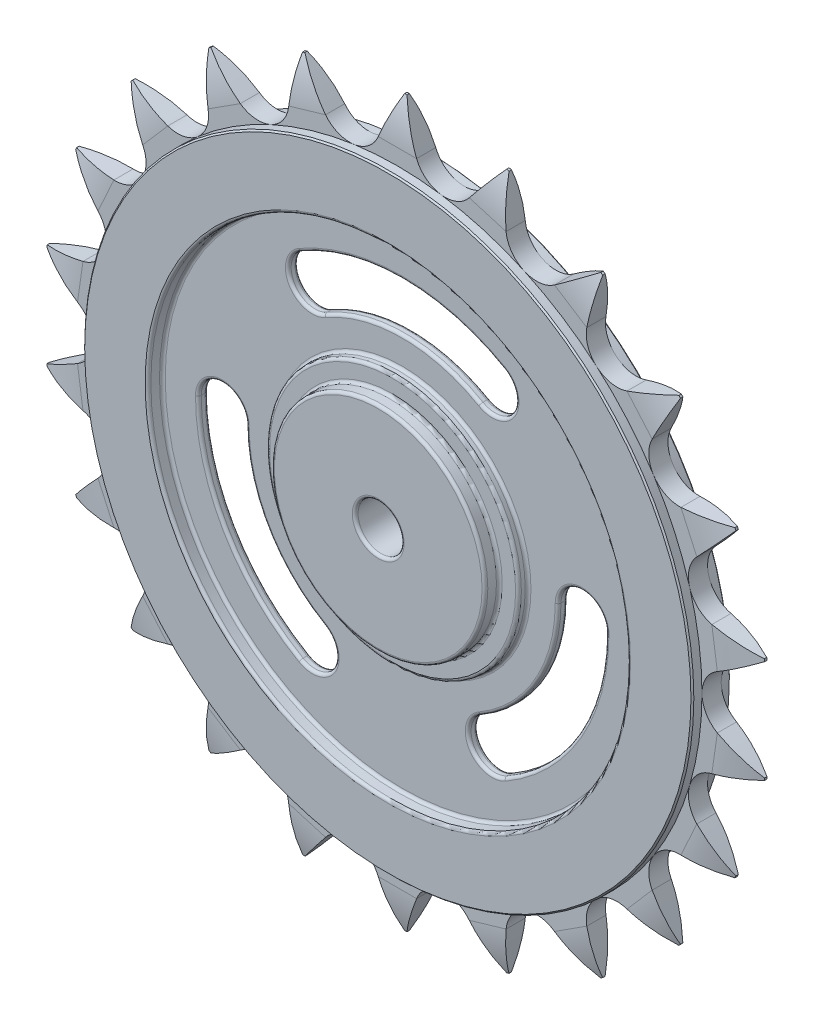
SolidWorks part; units mm, degrees
material "AISI 1020"
ref_plane "Спереди" through (0, 0, 0) normal (0, 0, 1) x (1, 0, 0)
ref_plane "Сверху" through (0, 0, 0) normal (0, 1, 0) x (1, 0, 0)
ref_plane "Справа" through (0, 0, 0) normal (1, 0, 0) x (0, 0, -1)
sketch "Эскиз1" plane through (0, 0, 0) normal (0, 0, 1) x (1, 0, 0)
  line L0 (0, 84.1537) -> (0, -82.6977) construction
  line L1 (-88.0817, 0) -> (85.9325, 0) construction
  line L3 (-46.0149, 53.1041) -> (-59.1121, 37.9891)
  line L4 (-59.1121, 37.9891) -> (-67.4204, 19.7964)
  line L5 (-67.4204, 19.7964) -> (-70.2667, 0)
  line L6 (-70.2667, 0) -> (-67.4204, -19.7964)
  line L7 (-67.4204, -19.7964) -> (-59.1121, -37.9891)
  line L8 (-59.1121, -37.9891) -> (-46.0149, -53.1041)
  line L9 (-46.0149, -53.1041) -> (-29.1899, -63.9169)
  line L10 (-29.1899, -63.9169) -> (-10, -69.5515)
  line L11 (-10, -69.5515) -> (10, -69.5515)
  line L12 (10, -69.5515) -> (29.1899, -63.9169)
  line L13 (29.1899, -63.9169) -> (46.0149, -53.1041)
  line L14 (46.0149, -53.1041) -> (59.1121, -37.9891)
  line L15 (59.1121, -37.9891) -> (67.4204, -19.7964)
  line L16 (67.4204, -19.7964) -> (70.2667, 0)
  line L17 (70.2667, 0) -> (67.4204, 19.7964)
  line L18 (67.4204, 19.7964) -> (59.1121, 37.9891)
  line L19 (59.1121, 37.9891) -> (46.0149, 53.1041)
  line L20 (46.0149, 53.1041) -> (29.1899, 63.9169)
  line L21 (29.1899, 63.9169) -> (10, 69.5515)
  line L22 (10, 69.5515) -> (-10, 69.5515)
  line L23 (-10, 69.5515) -> (-29.1899, 63.9169)
  line L24 (-29.1899, 63.9169) -> (-46.0149, 53.1041)
  circle A0 centre (0, 0) radius 69.5515 construction
  circle A1 centre (0, 0) radius 63.5 construction
  dimension "D2" = 127
  dimension "D1" = 20
sketch "Эскиз2" plane through (0, 0, 0) normal (0, 0, 1) x (1, 0, 0)
  line L0 (0, 98.4793) -> (0, -84.2006) construction
  line L1 (-81.0086, 0) -> (77.9699, 0) construction
  line L2 (-10, 69.5515) -> (10, 69.5515) construction
  line L3 (0, 84.1537) -> (0, -82.6977) construction
  line L4 (-88.0817, 0) -> (85.9325, 0) construction
  circle A0 centre (-10, 69.5515) radius 2.5 construction
  circle A1 centre (-10, 69.5515) radius 6 construction
  circle A2 centre (10, 69.5515) radius 6 construction
  circle A3 centre (10, 69.5515) radius 2.5 construction
  arc A4 (-7.5, 64.0972) -> (7.5, 64.0972) centre (0, 47.7341) cw construction
  arc A5 (-7.5, 75.0059) -> (7.5, 75.0059) centre (0, 91.369) ccw construction
  dimension "D1" = 5
  dimension "D2" = 12
  dimension "D3" = 18
sketch "Эскиз3" plane through (0, 0, 0) normal (0, 0, 1) x (1, 0, 0)
  line L0 (0, 101.2799) -> (0, -88.1727) construction
  line L1 (-91.1148, 0) -> (93.6517, 0) construction
  line L2 (-10, 69.5515) -> (0, 0) construction
  line L3 (0, 75.5515) -> (-0.25, 75.5515)
  line L4 (2, 75.5515) -> (-2, 75.5515) construction
  line L5 (10, 69.5515) -> (-10, 69.5515) construction
  line L6 (-2, 75.5515) -> (-5, 63.3028) construction
  line L7 (2, 75.5515) -> (5, 63.3028) construction
  circle A0 centre (0, 0) radius 63.5 construction
  arc A3 (-0.25, 75.5515) -> (-4, 66.8028) centre (204.0704, -17.2056) ccw
  arc A4 (-4, 66.8028) -> (-9.037, 62.8537) centre (-9.9502, 69.2052) cw
  dimension "D1" = 6
  dimension "D2" = 0.25
  dimension "D3" = 4
  dimension "D4" = 10
  dimension "D5" = 4
  dimension "D6" = 3.5
sketch "Эскиз4" plane through (0, 0, 0) normal (0, 0, 1) x (1, 0, 0)
  line L0 (0, 75.5515) -> (-0.25, 75.5515) construction
  line L1 (0.25, 75.5515) -> (-0.25, 75.5515)
  line L2 (0, 103.8753) -> (0, -7.6049) construction
  line L3 (0, 84.1537) -> (0, -82.6977) construction
  arc A0 (-0.25, 75.5515) -> (-4, 66.8028) centre (204.0704, -17.2056) ccw construction
  arc A1 (-9.037, 62.8537) -> (-4, 66.8028) centre (-9.9502, 69.2052) ccw construction
  arc A2 (-0.25, 75.5515) -> (-4, 66.8028) centre (204.0704, -17.2056) ccw
  arc A3 (-9.037, 62.8537) -> (-4, 66.8028) centre (-9.9502, 69.2052) ccw
  arc A4 (9.037, 62.8537) -> (4, 66.8028) centre (9.9502, 69.2052) cw
  arc A5 (0.25, 75.5515) -> (4, 66.8028) centre (-204.0704, -17.2056) cw
  circle A8 centre (0, 0) radius 63.5
  arc A9 (9.037, 62.8537) -> (-9.037, 62.8537) centre (0, 0) ccw
  dimension "D1" = 0
extrude "Бобышка-Вытянуть1" add sketch "Эскиз4" along normal mid plane 4
sketch "Эскиз5" plane through (0, 0, 0) normal (1, 0, 0) x (0, 0, -1)
  line L0 (0, 86.6638) -> (0, -5.1015) construction
  line L2 (0, 98.4793) -> (0, -84.2006) construction
  line L3 (0, 69.5515) -> (0, -69.5515) construction
  line L4 (-2, 66.8028) -> (-3, 66.8028)
  line L5 (-2, 66.8028) -> (2, 66.8028) construction
  line L6 (-0.25, 75.5515) -> (0.25, 75.5515)
  line L7 (-2, 75.5515) -> (2, 75.5515) construction
  line L8 (-2, 66.8028) -> (-2, 62.8537) construction
  line L9 (-3, 66.8028) -> (-3, 76.5515)
  line L10 (-3, 76.5515) -> (3, 76.5515)
  line L11 (-2, 75.5515) -> (-2, 66.8028) construction
  line L12 (2, 66.8028) -> (3, 66.8028)
  line L13 (3, 66.8028) -> (3, 76.5515)
  arc A0 (-0.25, 75.5515) -> (-2, 66.8028) centre (22.9959, 66.3523) ccw
  arc A1 (0.25, 75.5515) -> (2, 66.8028) centre (-22.9959, 66.3523) cw
  point P25 (0, 75.5515)
  point P26 (0, 76.5515)
  dimension "D1" = 25
  dimension "D2" = 1
  dimension "D3" = 1
  dimension "D4" = 0.5
extrude "Вырез-Вытянуть1" cut sketch "Эскиз5" against normal mid plane 12
ref_axis "Ось1" through (0, 0, 0) along (0, 0, 1)
pattern_circular "Круговой массив1" count 22 over 360 about axis through (0, 0, 0) along (0, 0, 1) of bodies 104
sketch "Эскиз6" plane through (0, 0, 0) normal (0, 0, 1) x (1, 0, 0)
  circle A0 centre (0, 0) radius 63.5 construction
  circle A1 centre (0, 0) radius 63.5
  circle A2 centre (0, 0) radius 50
  dimension "D1" = 100
extrude "Бобышка-Вытянуть2" add sketch "Эскиз6" along normal mid plane 8
sketch "Эскиз7" plane through (0, 0, 0) normal (0, 0, 1) x (1, 0, 0)
  line L0 (0, 84.1537) -> (0, -82.6977) construction
  line L1 (-18.75, 32.476) -> (0, 0) construction
  line L2 (0, 0) -> (18.75, 32.476) construction
  circle A1 centre (0, 0) radius 26.25
  circle A2 centre (0, 0) radius 50
  circle A3 centre (0, 0) radius 50
  arc A4 (-18.75, 32.476) -> (18.75, 32.476) centre (0, 0) cw construction
  arc A5 (21.25, 36.8061) -> (-21.25, 36.8061) centre (0, 0) ccw
  arc A6 (16.25, 28.1458) -> (-16.25, 28.1458) centre (0, 0) ccw
  arc A7 (16.25, 28.1458) -> (21.25, 36.8061) centre (18.75, 32.476) ccw
  arc A8 (-21.25, 36.8061) -> (-16.25, 28.1458) centre (-18.75, 32.476) ccw
  arc A9 (37.5, 0) -> (18.75, -32.476) centre (0, 0) cw construction
  arc A10 (21.25, -36.8061) -> (42.5, 0) centre (0, 0) ccw
  arc A11 (16.25, -28.1458) -> (32.5, 0) centre (0, 0) ccw
  arc A12 (16.25, -28.1458) -> (21.25, -36.8061) centre (18.75, -32.476) ccw
  arc A13 (42.5, 0) -> (32.5, 0) centre (37.5, 0) ccw
  arc A14 (-18.75, -32.476) -> (-37.5, 0) centre (0, 0) cw construction
  arc A15 (-42.5, 0) -> (-21.25, -36.8061) centre (0, 0) ccw
  arc A16 (-32.5, 0) -> (-16.25, -28.1458) centre (0, 0) ccw
  arc A17 (-32.5, 0) -> (-42.5, 0) centre (-37.5, 0) ccw
  arc A18 (-21.25, -36.8061) -> (-16.25, -28.1458) centre (-18.75, -32.476) ccw
  point P6 (0, 37.5)
  point P21 (32.476, -18.75)
  point P28 (-32.476, -18.75)
  point P33 (0, 0)
  dimension "D2" = 52.5
  dimension "D4" = 32.5
  dimension "D5" = 42.5
  dimension "D3" = 60
  dimension "D1" = 0
  dimension "D6" = 3
extrude "Бобышка-Вытянуть3" add sketch "Эскиз7" along normal mid plane 2
sketch "Эскиз8" plane through (0, 0, 0) normal (0, 0, 1) x (1, 0, 0)
  circle A2 centre (0, 0) radius 22.25
  circle A3 centre (0, 0) radius 22.25
  circle A5 centre (0, 0) radius 26.25
  circle A6 centre (0, 0) radius 26.25
  dimension "D1" = 4
  dimension "D2" = 0
extrude "Бобышка-Вытянуть4" add sketch "Эскиз8" along normal mid plane 6
sketch "Эскиз9" plane through (0, 0, 0) normal (0, 0, 1) x (1, 0, 0)
  circle A3 centre (0, 0) radius 4.8
  circle A5 centre (0, 0) radius 22.25
  circle A6 centre (0, 0) radius 22.25
  dimension "D1" = 9.6
  dimension "D2" = 0
extrude "Бобышка-Вытянуть5" add sketch "Эскиз9" along normal mid plane 12
chamfer "Фаска1" distance 0.3 angle 45 2 edges at (63.5, 0, -4) (63.5, 0, 4)
fillet "Скругление1" radius 0.6 38 edges at (4.8, 0, -6) (22.25, 0, -6) (22.25, 0, -3) (26.25, 0, -3) (-28.1458, -16.25, -1) (-14.4199, -34.976, -1) (-36.8061, -21.25, -1) (-37.5, 5, -1) (0, 32.5, -1) (-23.0801, 29.976, -1) (0, 42.5, -1) (23.0801, 29.976, -1) (50, 0, -1) (26.25, 0, -1) (28.1458, -16.25, -1) (37.5, 5, -1) (36.8061, -21.25, -1) (14.4199, -34.976, -1) (22.25, 0, 6) (4.8, 0, 6) (22.25, 0, 3) (26.25, 0, 3) (-14.4199, -34.976, 1) (-28.1458, -16.25, 1) (-37.5, 5, 1) (-36.8061, -21.25, 1) (37.5, 5, 1) (28.1458, -16.25, 1) (14.4199, -34.976, 1) (36.8061, -21.25, 1) (-23.0801, 29.976, 1) (0, 32.5, 1) (23.0801, 29.976, 1) (0, 42.5, 1) (26.25, 0, 1) (50, 0, 1) (50, 0, -4) (50, 0, 4)
